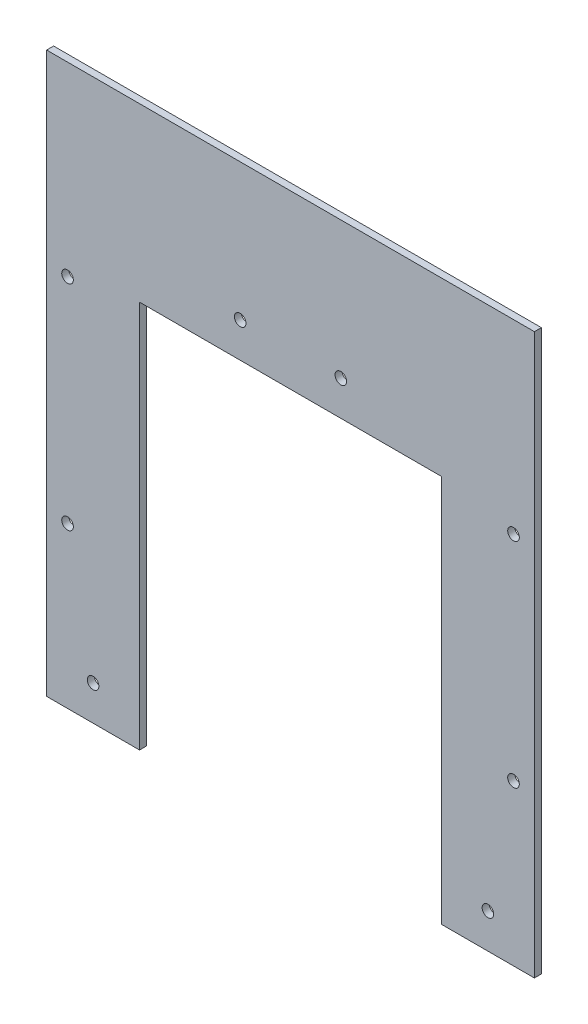
SolidWorks part; units mm, degrees
ref_plane "Alzado" through (0, 0, 0) normal (0, 0, 1) x (1, 0, 0)
ref_plane "Planta" through (0, 0, 0) normal (0, 1, 0) x (1, 0, 0)
ref_plane "Vista lateral" through (0, 0, 0) normal (1, 0, 0) x (0, 0, -1)
sketch "Croquis1" plane through (0, 0, 0) normal (0, 0, 1) x (1, 0, 0)
  line L0 (70, 0) -> (70, 167)
  line L1 (-100, 0) -> (-60, 0)
  line L2 (-100, 0) -> (-100, 241)
  line L3 (-100, 241) -> (110, 241)
  line L4 (110, 0) -> (110, 241)
  line L5 (70, 167) -> (-60, 167)
  line L6 (-60, 167) -> (-60, 0)
  line L7 (70, 0) -> (110, 0)
  circle A0 centre (-80, 15) radius 2.5
  circle A1 centre (-91, 69.01) radius 2.5
  circle A2 centre (-91, 161.01) radius 2.5
  circle A3 centre (-16.6667, 182) radius 2.5
  circle A4 centre (26.6667, 182) radius 2.5
  circle A5 centre (101, 161.01) radius 2.5
  circle A6 centre (101, 69.01) radius 2.5
  circle A7 centre (90, 15) radius 2.5
  dimension "D1" = 241
  dimension "D2" = 210
extrude "Saliente-Extruir1" add sketch "Croquis1" along normal blind 3
